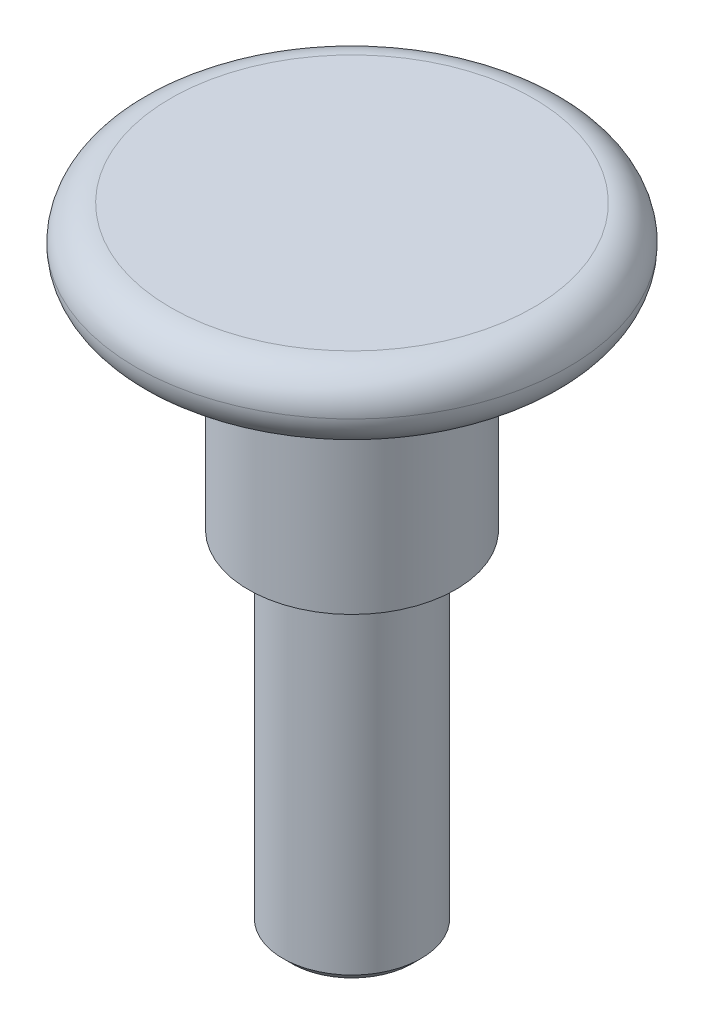
SolidWorks part; units mm, degrees
ref_plane "Plano frontal" through (0, 0, 0) normal (0, 0, 1) x (1, 0, 0)
ref_plane "Plano superior" through (0, 0, 0) normal (0, 1, 0) x (1, 0, 0)
ref_plane "Plano direito" through (0, 0, 0) normal (1, 0, 0) x (0, 0, -1)
sketch "Esboço1" plane through (0, 0, 0) normal (0, 0, 1) x (1, 0, 0)
  line L0 (0, -51.5243) -> (0, 58.9362) construction
  line L1 (0, 58.9362) -> (12.5, 58.9362)
  line L2 (12.5, 58.9362) -> (12.5, 54.9362)
  line L3 (12.5, 54.9362) -> (6, 54.9362)
  line L4 (6, 54.9362) -> (6, 42.5362)
  line L5 (6, 42.5362) -> (4, 42.5362)
  line L6 (4, 42.5362) -> (4, 22.5362)
  line L7 (4, 22.5362) -> (1.75, 22.5362)
  line L8 (0, 58.9362) -> (0, 31.7862)
  line L9 (1.75, 22.5362) -> (1.75, 30.5362)
  line L10 (1.75, 30.5362) -> (0, 31.7862)
  dimension "D1" = 12.5
  dimension "D2" = 1.75
  dimension "D3" = 8
  dimension "D4" = 4
  dimension "D5" = 12.4
  dimension "D6" = 20
  dimension "D7" = 8
  dimension "D8" = 9.25
revolve "Revolução1" add sketch "Esboço1" angle 360 about L0
fillet "Filete1" radius 2 2 edges at (0, 54.9362, -12.5) (0, 58.9362, -12.5)
chamfer "Chanfro1" distance 0.5 angle 45 1 edges at (0, 22.5362, -4)
